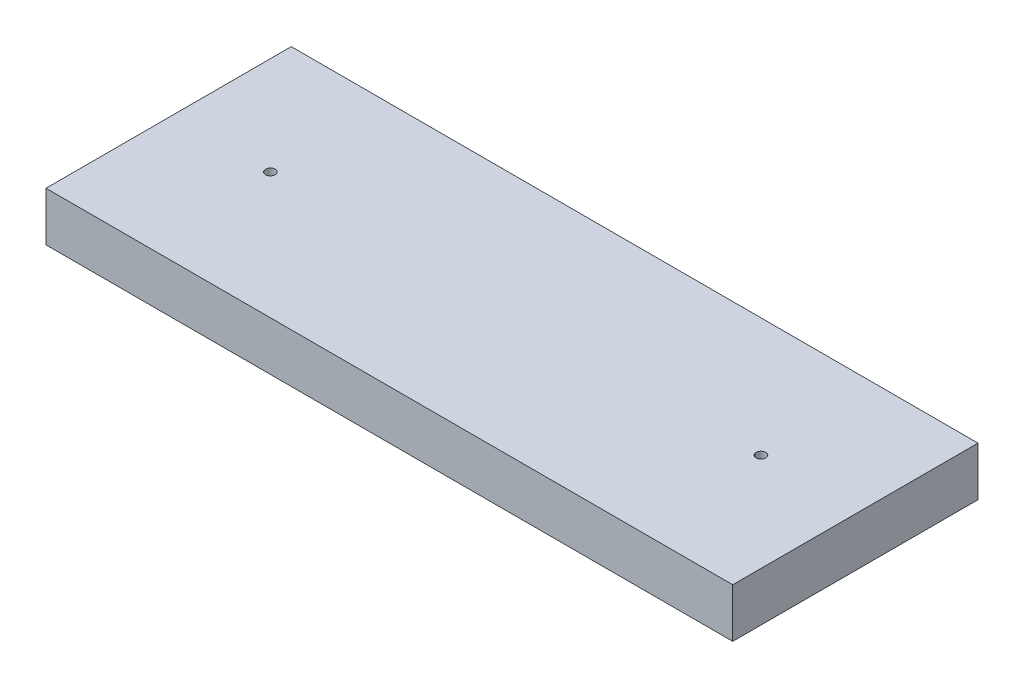
SolidWorks part; units mm, degrees
ref_plane "Front Plane" through (0, 0, 0) normal (0, 0, 1) x (1, 0, 0)
ref_plane "Top Plane" through (0, 0, 0) normal (0, 1, 0) x (1, 0, 0)
ref_plane "Right Plane" through (0, 0, 0) normal (1, 0, 0) x (0, 0, -1)
sketch "Sketch1" plane through (0, 0, 0) normal (0, 1, 0) x (1, 0, 0)
  line L1 (355.6, -127) -> (-355.6, -127)
  line L2 (355.6, -127) -> (355.6, 127)
  line L3 (355.6, 127) -> (-355.6, 127)
  line L4 (-355.6, -127) -> (-355.6, 127)
  line L5 (355.6, -127) -> (-355.6, 127) construction
  line L6 (355.6, 127) -> (-355.6, -127) construction
  point P0 (0, 0)
  point P5 (0, 0)
  point P6 (0, 0)
  dimension "D1" = 711.2
  dimension "D2" = 254
extrude "Boss-Extrude1" add sketch "Sketch1" along normal blind 50.8 contours L4 L3 L2 L1
hole_wizard "Ø10.0mm Dowel Hole1" positions "Sketch2" profile "Sketch3" hole size "Ø10.0" standard "ANSI Metric" end condition through all
sketch "Sketch2" plane through (0, 50.8, 0) normal (0, 1, 0) x (1, 0, 0)
  line L1 (-355.6, -127) -> (-355.6, 127) construction
  line L2 (355.6, -127) -> (355.6, 127) construction
  line L3 (-254, 3.81) -> (254, 3.81) construction
  line L5 (355.6, -127) -> (-355.6, -127) construction
  point P0 (-254, 3.81)
  point P2 (254, 3.81)
  dimension "D1" = 101.6
  dimension "D2" = 101.6
  dimension "D3" = 130.81
sketch "Sketch3" plane through (-254, 50.8, -3.81) normal (1, 0, 0) x (0, 0, 1)
  line L0 (0, 0) -> (0, 50.8)
  line L1 (0, 50.8) -> (5, 50.8)
  line L2 (5, 50.8) -> (5, 0)
  line L5 (5, 0) -> (0, 0)
  line L11 (0, -6.35) -> (0, 107.95) construction
  dimension "Thru Hole Dia." = 10
  dimension "Thru Hole Depth" = 50.8
